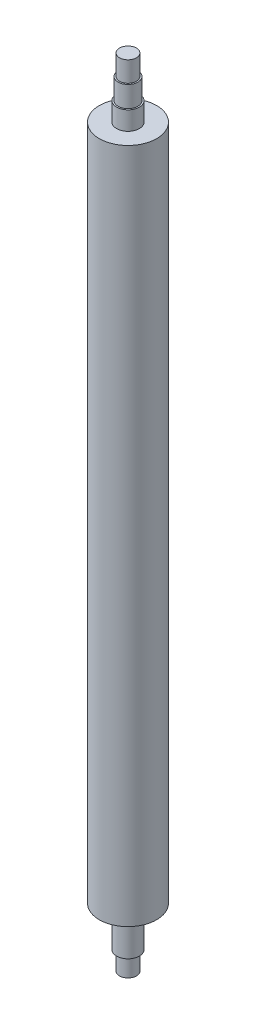
SolidWorks part; units mm, degrees
material "Stainless Steel (ferritic)"
ref_plane "Front Plane" through (0, 0, 0) normal (0, 0, 1) x (1, 0, 0)
ref_plane "Top Plane" through (0, 0, 0) normal (0, 1, 0) x (1, 0, 0)
ref_plane "Right Plane" through (0, 0, 0) normal (1, 0, 0) x (0, 0, -1)
sketch "Sketch1" plane through (0, 0, 0) normal (0, 1, 0) x (1, 0, 0)
  circle A0 centre (0, 0) radius 3.965
  circle A1 centre (0, 0) radius 3.45
  circle A2 centre (0, 0) radius 2.95
  circle A3 centre (0, 0) radius 10
  dimension "D1" = 7.93
  dimension "D2" = 6.9
  dimension "D3" = 5.9
  dimension "D4" = 20
extrude "Boss-Extrude8" add sketch "Sketch1" along normal blind 236 contours A3
extrude "Boss-Extrude9" add sketch "Sketch1<9>" against normal blind 14 contours A0
sketch "Sketch1<9>" plane through (0, 0, 0) normal (0, 1, 0) x (1, 0, 0) same geometry as "Sketch1"
extrude "Boss-Extrude10" add sketch "Sketch1<10>" against normal blind 6.5 from surface contours A2 region at (0, 0, 0) starting at face at (0, -14, 3.965)
sketch "Sketch1<10>" plane through (0, 0, 0) normal (0, 1, 0) x (1, 0, 0) same geometry as "Sketch1"
extrude "Boss-Extrude11" add sketch "Sketch1<11>" along normal blind 6.5 from surface contours A0 starting at face at (0, 236, 10)
sketch "Sketch1<11>" plane through (0, 0, 0) normal (0, 1, 0) x (1, 0, 0) same geometry as "Sketch1"
extrude "Boss-Extrude12" add sketch "Sketch1<12>" along normal blind 7.3 from surface contours A1 starting at face at (0, 242.5, 3.965)
sketch "Sketch1<12>" plane through (0, 0, 0) normal (0, 1, 0) x (1, 0, 0) same geometry as "Sketch1"
extrude "Boss-Extrude13" add sketch "Sketch1<13>" along normal blind 7.1 from surface contours A2 starting at face at (0, 249.8, 3.45)
sketch "Sketch1<13>" plane through (0, 0, 0) normal (0, 1, 0) x (1, 0, 0) same geometry as "Sketch1"
